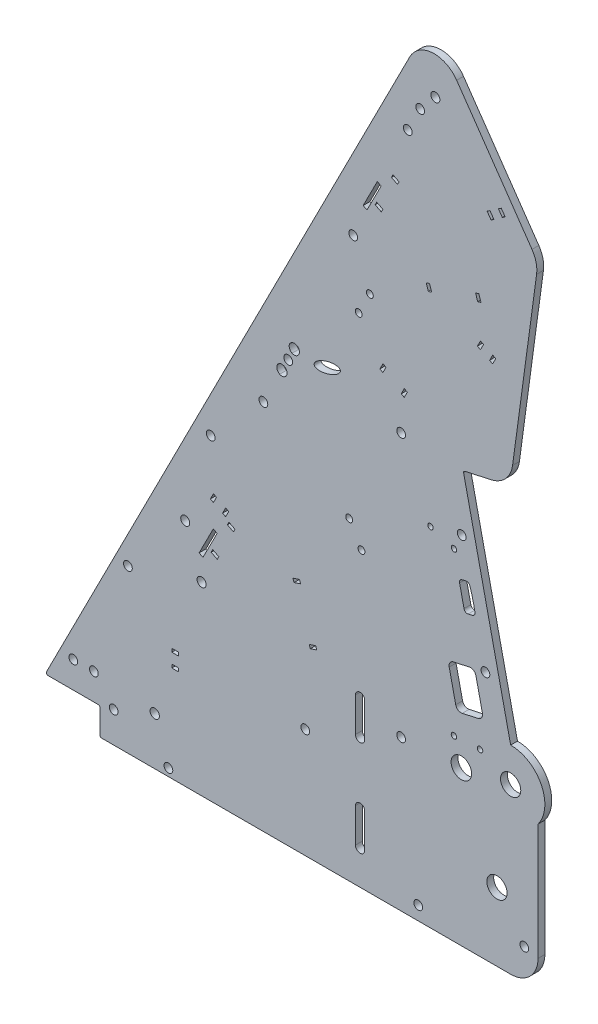
SolidWorks part; units mm, degrees
other "Markup1"
sketch "Sketch5"
ref_plane "Front Plane" through (0, 0, 0) normal (0, 0, 1) x (1, 0, 0)
ref_plane "Top Plane" through (0, 0, 0) normal (0, 1, 0) x (1, 0, 0)
ref_plane "Right Plane" through (0, 0, 0) normal (1, 0, 0) x (0, 0, -1)
sketch "Sketch1" plane through (0, 0, 0) normal (0, 0, 1) x (1, 0, 0)
  line L1 (228.6, -12.7) -> (228.6, 53.975)
  line L2 (178.7547, 351.4131) -> (0, 0)
  line L3 (228.6, 279.4) -> (178.7547, 351.4131)
  line L5 (0, 0) -> (25.4, 0)
  line L6 (25.4, 0) -> (25.4, -12.7)
  line L7 (25.4, -12.7) -> (228.6, -12.7)
  line L9 (215.9, 79.375) -> (193.9097, 178.5667)
  line L10 (193.9097, 178.5667) -> (215.6079, 183.377)
  line L11 (215.6079, 183.377) -> (228.6, 279.4)
  arc A0 (228.6, 53.975) -> (215.9, 79.375) centre (215.9, 63.5) ccw
  dimension "D7" = 12.7
  dimension "D8" = 76.2
  dimension "D10" = 31.75
  dimension "D2" = 292.1
  dimension "D3" = 25.4
  dimension "D4" = 215.9
  dimension "D5" = 394.2644
  dimension "D6" = 203.2
  dimension "D9" = 63.039
  dimension "D11" = 101.6
  dimension "D12" = 12.5
  dimension "D13" = 22.225
extrude "Boss-Extrude1" add sketch "Sketch1" along normal blind 3.175
sketch "Sketch2" plane through (0, 0, 3.175) normal (0, 0, 1) x (1, 0, 0)
  line L0 (178.7547, 351.4131) -> (0, 0) construction
  line L1 (25.4, -12.7) -> (228.6, -12.7) construction
  line L2 (215.9, 79.375) -> (193.9097, 178.5667) construction
  line L3 (193.9097, 178.5667) -> (215.6079, 183.377) construction
  line L4 (215.9, 79.375) -> (193.9097, 178.5667) construction
  line L5 (64.9432, 94.0578) -> (72.5445, 73.1732) construction
  line L6 (64.9432, 94.0578) -> (89.8317, 94.0578) construction
  line L10 (228.6, -12.7) -> (228.6, 53.975) construction
  circle A0 centre (64.9432, 94.0578) radius 2.0955
  circle A1 centre (180.975, 322.1643) radius 2.0955
  circle A2 centre (72.5445, 73.1732) radius 2.0955
  circle A3 centre (193.2078, 152.3944) radius 2.032
  circle A4 centre (215.9, 63.5) radius 4.699
  circle A7 centre (173.0375, -6.35) radius 2.032
  circle A8 centre (204.203, 102.7985) radius 2.032
  circle A26 centre (209.55, 19.05) radius 4.699
  arc A30 (228.6, 53.975) -> (215.9, 79.375) centre (215.9, 63.5) ccw construction
  circle A31 centre (165.1, 179.3875) radius 2.032
  dimension "D3" = 4.191
  dimension "D5" = 4.191
  dimension "D9" = 4.191
  dimension "D20" = 9.398
  dimension "D23" = 9.398
  dimension "D18" = 4.064
  dimension "D26" = 4.064
  dimension "D14" = 4.064
  dimension "D2" = 15.24
  dimension "D6" = 15.24
  dimension "D7" = 22.225
  dimension "D21" = 44.45
  dimension "D22" = 6.35
  dimension "D19" = 160.3375
  dimension "D24" = 44.45
  dimension "D25" = 6.35
  dimension "D27" = 25.4
  dimension "D28" = 50.8
  dimension "D29" = 6.35
  dimension "D17" = 6.35
  dimension "D33" = 55.5625
  dimension "D15" = 114.3
  dimension "D4" = 180.975
  dimension "D8" = 70
extrude "Cut-Extrude1" cut sketch "Sketch2" against normal through all
sketch "Sketch7" plane through (0, 0, 3.175) normal (0, 0, 1) x (1, 0, 0)
  line L0 (146.05, 3.175) -> (146.05, 19.05) construction
  line L1 (143.891, 3.175) -> (143.891, 19.05)
  line L2 (148.209, 3.175) -> (148.209, 19.05)
  line L3 (146.05, 47.625) -> (146.05, 63.5) construction
  line L4 (143.891, 47.625) -> (143.891, 63.5)
  line L5 (148.209, 47.625) -> (148.209, 63.5)
  line L6 (25.4, -12.7) -> (228.6, -12.7) construction
  line L12 (228.6, -12.7) -> (228.6, 53.975) construction
  line L13 (25.4, -12.7) -> (228.6, -12.7) construction
  arc A0 (143.891, 3.175) -> (148.209, 3.175) centre (146.05, 3.175) ccw
  arc A1 (148.209, 19.05) -> (143.891, 19.05) centre (146.05, 19.05) ccw
  arc A2 (143.891, 47.625) -> (148.209, 47.625) centre (146.05, 47.625) ccw
  arc A3 (148.209, 63.5) -> (143.891, 63.5) centre (146.05, 63.5) ccw
  circle A8 centre (50.8, 9.525) radius 2.159
  point P2 (146.05, 11.1125)
  point P9 (146.05, 55.5625)
  dimension "D1" = 4.318
  dimension "D5" = 4.318
  dimension "D2" = 15.875
  dimension "D3" = 15.875
  dimension "D4" = 44.45
  dimension "D6" = 95.25
  dimension "D7" = 82.55
  dimension "D8" = 15.875
  dimension "D9" = 22.225
extrude "Cut-Extrude2" cut sketch "Sketch7" against normal through all
sketch "Sketch10" plane through (0, 0, 3.175) normal (0, 0, 1) x (1, 0, 0)
  circle A1 centre (165.1, 57.15) radius 2.032
  circle A2 centre (120.65, 38.1) radius 2.032
  circle A3 centre (13.0465, 12.3347) radius 2.032
  circle A4 centre (22.5715, 12.3347) radius 2.032
  circle A5 centre (38.3604, 62.564) radius 2.032
  dimension "D1" = 4.064
  dimension "D2" = 4.064
  dimension "D4" = 63.5
  dimension "D5" = 69.85
extrude "Cut-Extrude3" cut sketch "Sketch10" against normal up to next
fillet "Fillet1" radius 12.7 4 edges at (228.6, -12.7, 1.5875) (178.7547, 351.4131, 1.5875) (215.6079, 183.377, 1.5875) (228.6, 279.4, 1.5875)
fillet "Fillet2" radius 0.7937 4 edges at (25.4, -12.7, 1.5875) (25.4, 0, 1.5875) (193.9097, 178.5667, 1.5875) (0, 0, 1.5875)
sketch "Sketch12" plane through (0, 0, 3.175) normal (0, 0, 1) x (1, 0, 0)
  circle A0 centre (31.75, 1.5875) radius 2.032
  circle A1 centre (222.25, 1.5875) radius 2.032
  circle A2 centre (57.15, -9.2075) radius 2.032
  circle A3 centre (57.15, -9.2075) radius 2.286 construction
  dimension "D1" = 4.064
  dimension "D2" = 4.064
extrude "Cut-Extrude5" cut sketch "Sketch12" against normal through all
sketch "Sketch13" plane through (0, 0, 3.175) normal (0, 0, 1) x (1, 0, 0)
  line L2 (194.6847, 178.7385) -> (206.9592, 181.4597) construction
  line L5 (199.2434, 101.699) -> (189.6226, 145.0954) construction
  line L6 (189.6022, 69.9806) -> (201.7089, 70.5092) construction
  line L7 (186.8444, 98.9502) -> (199.2434, 101.699)
  line L8 (186.8444, 98.9502) -> (190.9676, 80.3518)
  line L9 (190.9676, 80.3518) -> (203.3665, 83.1006)
  line L10 (199.2434, 101.699) -> (203.3665, 83.1006)
  line L11 (189.6022, 69.9806) -> (190.9676, 80.3518) construction
  line L12 (201.7089, 70.5092) -> (203.3665, 83.1006) construction
  line L13 (215.9, 79.375) -> (194.0815, 177.7917) construction
  line L14 (178.7216, 148.5324) -> (189.6226, 145.0954) construction
  line L15 (195.1281, 134.9336) -> (193.4153, 134.5539)
  line L16 (192.209, 132.6604) -> (194.2706, 123.3612)
  line L17 (196.1641, 122.1549) -> (198.1091, 122.5861)
  line L18 (211.4332, 99.5233) -> (205.2337, 98.1489) construction
  line L19 (198.3765, 158.4184) -> (211.4332, 99.5233) construction
  circle A0 centre (189.6022, 69.9806) radius 1.27
  circle A1 centre (201.7089, 70.5092) radius 1.27
  circle A2 centre (178.7216, 148.5324) radius 1.27
  circle A3 centre (189.6226, 145.0954) radius 1.27
  arc A4 (199.3306, 124.402) -> (196.9796, 133.88) centre (134.9024, 113.4517) ccw
  arc A6 (199.4957, 103.5221) -> (189.2475, 149.7492) centre (134.9024, 113.4517) ccw construction
  arc A7 (195.1281, 134.9336) -> (196.9796, 133.88) centre (195.4717, 133.3837) cw
  arc A8 (198.1091, 122.5861) -> (199.3306, 124.402) centre (197.7655, 124.136) ccw
  arc A9 (194.2706, 123.3612) -> (196.1641, 122.1549) centre (195.8205, 123.7048) ccw
  arc A10 (193.4153, 134.5539) -> (192.209, 132.6604) centre (193.7589, 133.004) ccw
  point P26 (208.3335, 98.8361)
  point P31 (196.515, 135.2411)
  point P36 (194.6142, 121.8113)
  point P39 (191.8654, 134.2103)
  dimension "D7" = 2.54
  dimension "D16" = 1.5875
  dimension "D2" = 11.43
  dimension "D3" = 76.2
  dimension "D4" = 12.7
  dimension "D5" = 19.05
  dimension "D6" = 120
  dimension "D8" = 110
  dimension "D9" = 80
  dimension "D10" = 12.7
  dimension "D11" = 44.45
  dimension "D12" = 11.43
  dimension "D13" = 12.7
  dimension "D14" = 4.7625
  dimension "D15" = 38.1
extrude "Cut-Extrude6" cut sketch "Sketch13" against normal through all both and the other way through all
sketch "Sketch14" plane through (0, 0, 3.175) normal (0, 0, 1) x (1, 0, 0)
  line L0 (26.1937, -12.7) -> (215.9, -12.7) construction
  line L1 (228.6, 0) -> (228.6, 53.975) construction
  line L2 (112.7125, 182.5625) -> (101.1964, 159.9231) construction
  line L3 (169.1053, 332.4434) -> (0.5868, 1.1536) construction
  line L4 (112.7125, 182.5625) -> (136.864, 190.4279) construction
  line L5 (147.4827, 261.9243) -> (154.0469, 274.8287)
  line L6 (147.4827, 261.9243) -> (149.2654, 261.0175)
  line L7 (154.0469, 274.8287) -> (155.8295, 273.922)
  line L8 (149.2654, 261.0175) -> (155.8295, 273.922)
  line L9 (169.1053, 332.4434) -> (0.5868, 1.1536) construction
  line L10 (160.5905, 279.7801) -> (161.3102, 281.1951)
  line L11 (160.5905, 279.7801) -> (163.4204, 278.3406)
  line L12 (161.3102, 281.1951) -> (164.1402, 279.7556)
  line L13 (163.4204, 278.3406) -> (164.1402, 279.7556)
  line L14 (153.7897, 266.4104) -> (156.6196, 264.9709)
  line L15 (153.7897, 266.4104) -> (153.0699, 264.9954)
  line L16 (156.6196, 264.9709) -> (155.8998, 263.5559)
  line L17 (153.0699, 264.9954) -> (155.8998, 263.5559)
  line L19 (178.2697, 245.9923) -> (179.2404, 242.9693)
  line L20 (178.2697, 245.9923) -> (176.7582, 245.5069)
  line L21 (179.2404, 242.9693) -> (177.7289, 242.4839)
  line L22 (176.7582, 245.5069) -> (177.7289, 242.4839)
  line L24 (200.6096, 249.8308) -> (199.639, 252.8538)
  line L25 (200.6096, 249.8308) -> (202.1211, 250.3161)
  line L26 (199.639, 252.8538) -> (201.1505, 253.3391)
  line L27 (202.1211, 250.3161) -> (201.1505, 253.3391)
  line L34 (77.9534, 97.2255) -> (79.736, 96.3187)
  line L47 (77.9534, 97.2255) -> (71.3892, 84.3211)
  line L56 (79.736, 96.3187) -> (73.1718, 83.4143)
  line L57 (71.3892, 84.3211) -> (73.1718, 83.4143)
  line L58 (85.2167, 103.5918) -> (84.497, 102.1769)
  line L59 (85.2167, 103.5918) -> (88.0466, 102.1523)
  line L60 (84.497, 102.1769) -> (87.3269, 100.7374)
  line L61 (88.0466, 102.1523) -> (87.3269, 100.7374)
  line L62 (156.643, 199.3999) -> (158.0826, 202.2298)
  line L63 (156.643, 199.3999) -> (155.2281, 200.1197)
  line L64 (158.0826, 202.2298) -> (156.6676, 202.9496)
  line L65 (155.2281, 200.1197) -> (156.6676, 202.9496)
  line L66 (165.1328, 195.0814) -> (166.5723, 197.9113)
  line L67 (165.1328, 195.0814) -> (166.5478, 194.3617)
  line L68 (166.5723, 197.9113) -> (167.9873, 197.1916)
  line L69 (166.5478, 194.3617) -> (167.9873, 197.1916)
  line L78 (77.6961, 88.8072) -> (76.9764, 87.3922)
  line L79 (201.9154, 234.7497) -> (200.4759, 231.9198)
  line L80 (201.9154, 234.7497) -> (203.3303, 234.0299)
  line L81 (200.4759, 231.9198) -> (201.8908, 231.2)
  line L82 (203.3303, 234.0299) -> (201.8908, 231.2)
  line L83 (206.1357, 229.0407) -> (207.5752, 231.8707)
  line L84 (206.1357, 229.0407) -> (207.5507, 228.321)
  line L85 (207.5752, 231.8707) -> (208.9902, 231.1509)
  line L86 (207.5507, 228.321) -> (208.9902, 231.1509)
  line L88 (205.014, 288.3715) -> (206.821, 285.7609)
  line L89 (205.014, 288.3715) -> (206.3193, 289.275)
  line L90 (206.821, 285.7609) -> (208.1263, 286.6644)
  line L91 (206.3193, 289.275) -> (208.1263, 286.6644)
  line L92 (210.2352, 291.9855) -> (212.0422, 289.3749)
  line L93 (210.2352, 291.9855) -> (211.5405, 292.889)
  line L94 (212.0422, 289.3749) -> (213.3475, 290.2784)
  line L95 (211.5405, 292.889) -> (213.3475, 290.2784)
  line L96 (225.7968, 283.4499) -> (190.8675, 333.9133) construction
  line L97 (77.6961, 88.8072) -> (80.5261, 87.3677)
  line L98 (76.9764, 87.3922) -> (79.8063, 85.9527)
  line L99 (80.5261, 87.3677) -> (79.8063, 85.9527)
  line L100 (122.4534, 73.1037) -> (122.9512, 71.5963)
  line L101 (122.4534, 73.1037) -> (125.4682, 74.0993)
  line L102 (122.9512, 71.5963) -> (125.9661, 72.5919)
  line L103 (125.4682, 74.0993) -> (125.9661, 72.5919)
  line L104 (114.9173, 95.9228) -> (115.4151, 94.4154)
  line L105 (114.9173, 95.9228) -> (117.9322, 96.9185)
  line L106 (115.4151, 94.4154) -> (118.43, 95.411)
  line L107 (117.9322, 96.9185) -> (118.43, 95.411)
  line L108 (73.3338, 88.1438) -> (77.899, 97.1186) construction
  line L109 (75.1164, 87.2371) -> (79.6816, 96.2118) construction
  line L110 (76.2812, 89.5269) -> (86.5313, 84.313) construction
  line L111 (83.082, 102.8966) -> (93.3321, 97.6827) construction
  line L112 (121.934, 72.0825) -> (123.4755, 75.113) construction
  line L113 (127.9171, 72.8537) -> (123.4755, 75.113) construction
  line L114 (112.3753, 83.5081) -> (119.5388, 97.5909) construction
  line L115 (112.1491, 96.0767) -> (117.4079, 93.4017) construction
  line L116 (149.0052, 264.9173) -> (147.5544, 262.0651) construction
  line L117 (150.7878, 264.0106) -> (151.2099, 264.8403) construction
  line L118 (162.6248, 261.9162) -> (152.3747, 267.1302) construction
  line L119 (169.4256, 275.2859) -> (159.1755, 280.4999) construction
  line L120 (199.3876, 252.3597) -> (200.1584, 253.8749) construction
  line L121 (198.6169, 250.8445) -> (203.0585, 248.5852) construction
  line L122 (203.2698, 247.9167) -> (195.3067, 232.262) construction
  line L123 (180.2625, 244.9786) -> (175.0037, 247.6536) construction
  line L124 (178.1316, 240.7894) -> (185.2951, 254.8722) construction
  line L125 (190.7763, 226.1672) -> (185.5176, 228.8422) construction
  line L126 (58.7375, 39.6875) -> (61.9125, 39.6875)
  line L127 (58.7375, 39.6875) -> (58.7375, 38.1)
  line L128 (61.9125, 39.6875) -> (61.9125, 38.1)
  line L129 (58.7375, 38.1) -> (61.9125, 38.1)
  line L130 (58.7375, 33.3375) -> (61.9125, 33.3375)
  line L131 (58.7375, 33.3375) -> (58.7375, 31.75)
  line L132 (61.9125, 33.3375) -> (61.9125, 31.75)
  line L133 (58.7375, 31.75) -> (61.9125, 31.75)
  line L135 (78.0516, 111.4242) -> (76.6121, 108.5943)
  line L136 (78.0516, 111.4242) -> (79.4665, 110.7045)
  line L137 (76.6121, 108.5943) -> (78.027, 107.8745)
  line L138 (79.4665, 110.7045) -> (78.027, 107.8745)
  line L139 (82.2719, 105.7153) -> (83.7114, 108.5452)
  line L140 (82.2719, 105.7153) -> (83.6869, 104.9955)
  line L141 (83.7114, 108.5452) -> (85.1264, 107.8254)
  line L142 (83.6869, 104.9955) -> (85.1264, 107.8254)
  circle A0 centre (142.875, 247.65) radius 2.032
  circle A1 centre (112.7125, 182.5625) radius 2.032
  circle A2 centre (101.1964, 159.9231) radius 2.032
  circle A3 centre (150.594, 227.8985) radius 1.6 construction
  circle A4 centre (145.4254, 217.7376) radius 1.6 construction
  circle A5 centre (141.0058, 132.9805) radius 1.6 construction
  circle A6 centre (146.7058, 123.1078) radius 1.6 construction
  circle A7 centre (150.594, 227.8985) radius 1.6
  circle A8 centre (145.4254, 217.7376) radius 1.6
  circle A9 centre (141.0058, 132.9805) radius 1.6
  circle A10 centre (146.7058, 123.1078) radius 1.6
  arc A13 (0, 1.5875) -> (1.5875, 0) centre (1.5875, 1.5875) ccw construction
  ellipse E0 centre (109.8335, 176.9027) end of major axis (108.7539, 174.7802) minor radius 2.32 (108.7539, 174.7802) -> (110.9131, 179.0251) ccw construction
  ellipse E1 centre (109.8335, 176.9027) end of major axis (108.7539, 174.7802) minor radius 2.32 (108.7539, 174.7802) -> (110.9131, 179.0251) ccw
  ellipse E2 centre (130.8261, 188.4615) end of major axis (124.7883, 186.4952) minor radius 2.3812
  ellipse E3 centre (115.5915, 188.2223) end of major axis (114.5119, 186.0999) minor radius 2.32 (114.5119, 186.0999) -> (116.6711, 190.3448) ccw construction
  ellipse E4 centre (115.5915, 188.2223) end of major axis (114.5119, 186.0999) minor radius 2.32 (114.5119, 186.0999) -> (116.6711, 190.3448) ccw
  spline S0 degree 3 poles (603.8918, 1049.0657) (-166.9189, -675.3083) (147.8077, 168.3802) (110.3225, 179.2425) (110.1654, 179.2721) (109.6955, 179.3152) (109.3734, 179.2831) (108.9218, 179.1456) (108.7737, 179.0841) (108.4954, 178.9343) (108.365, 178.8464) (108.1219, 178.6442) (108.0097, 178.5297) (107.8134, 178.2839) (107.7278, 178.1512) (107.5834, 177.8672) (107.527, 177.7202) (107.4441, 177.4168) (107.4178, 177.2585) (107.3978, 176.9432) (107.4036, 176.7863) (107.4465, 176.4736) (107.4841, 176.3175) (107.5874, 176.0205) (107.6532, 175.8777) (107.8133, 175.6037) (107.9066, 175.4748) (114.8282, 167.6036) (173.9427, 200.577) (-567.4982, 911.3293) knots -15.287416 -15.287416 -15.287416 -15.287416 0.0625 0.0625 0.125 0.125 0.25 0.25 0.3125 0.3125 0.375 0.375 0.4375 0.4375 0.5 0.5 0.5625 0.5625 0.625 0.625 0.6875 0.6875 0.75 0.75 0.8125 0.8125 0.875 0.875 4.983329 4.983329 4.983329 4.983329 only from (110.9131, 179.0251) to (108.7539, 174.7802) construction
  spline S1 degree 3 poles (110.9131, 179.0251) (110.7727, 179.0965) (110.6265, 179.1544) (110.3225, 179.2425) (110.1654, 179.2721) (109.6955, 179.3152) (109.3734, 179.2831) (108.9218, 179.1456) (108.7737, 179.0841) (108.4954, 178.9343) (108.365, 178.8464) (108.1219, 178.6442) (108.0097, 178.5297) (107.8134, 178.2839) (107.7278, 178.1512) (107.5834, 177.8672) (107.527, 177.7202) (107.4441, 177.4168) (107.4178, 177.2585) (107.3978, 176.9432) (107.4036, 176.7863) (107.4465, 176.4736) (107.4841, 176.3175) (107.5874, 176.0205) (107.6532, 175.8777) (107.8133, 175.6037) (107.9066, 175.4748) (108.2178, 175.121) (108.4736, 174.9228) (108.7539, 174.7802) knots 0 0 0 0 0.0625 0.0625 0.125 0.125 0.25 0.25 0.3125 0.3125 0.375 0.375 0.4375 0.4375 0.5 0.5 0.5625 0.5625 0.625 0.625 0.6875 0.6875 0.75 0.75 0.8125 0.8125 0.875 0.875 1 1 1 1
  spline S2 degree 3 poles (-635.3332, 847.705) (160.0375, 206.8561) (120.8424, 181.1302) (113.9875, 186.4501) (113.8729, 186.5577) (113.5583, 186.9155) (113.3974, 187.1901) (113.2413, 187.6401) (113.2046, 187.793) (113.1618, 188.1044) (113.1558, 188.2648) (113.176, 188.5797) (113.2018, 188.7347) (113.2848, 189.0394) (113.3426, 189.1891) (113.5563, 189.6095) (113.7586, 189.8627) (114.1212, 190.1647) (114.2542, 190.2544) (114.5324, 190.4041) (114.6775, 190.4645) (114.9798, 190.5567) (115.1369, 190.5882) (115.4499, 190.6199) (115.6074, 190.6207) (115.9244, 190.5918) (116.0795, 190.5623) (125.0451, 187.9725) (125.4505, 134.6135) (-868.6048, 361.2821) knots -3.325634 -3.325634 -3.325634 -3.325634 0.0625 0.0625 0.125 0.125 0.25 0.25 0.3125 0.3125 0.375 0.375 0.4375 0.4375 0.5 0.5 0.625 0.625 0.6875 0.6875 0.75 0.75 0.8125 0.8125 0.875 0.875 0.9375 0.9375 4.586013 4.586013 4.586013 4.586013 only from (114.5119, 186.0999) to (116.6711, 190.3448) construction
  spline S3 degree 3 poles (114.5119, 186.0999) (114.3711, 186.1715) (114.2359, 186.2574) (113.9875, 186.4501) (113.8729, 186.5577) (113.5583, 186.9155) (113.3974, 187.1901) (113.2413, 187.6401) (113.2046, 187.793) (113.1618, 188.1044) (113.1558, 188.2648) (113.176, 188.5797) (113.2018, 188.7347) (113.2848, 189.0394) (113.3426, 189.1891) (113.5563, 189.6095) (113.7586, 189.8627) (114.1212, 190.1647) (114.2542, 190.2544) (114.5324, 190.4041) (114.6775, 190.4645) (114.9798, 190.5567) (115.1369, 190.5882) (115.4499, 190.6199) (115.6074, 190.6207) (115.9244, 190.5918) (116.0795, 190.5623) (116.3815, 190.4751) (116.53, 190.4166) (116.6711, 190.3448) knots 0 0 0 0 0.0625 0.0625 0.125 0.125 0.25 0.25 0.3125 0.3125 0.375 0.375 0.4375 0.4375 0.5 0.5 0.625 0.625 0.6875 0.6875 0.75 0.75 0.8125 0.8125 0.875 0.875 0.9375 0.9375 1 1 1 1
  point P179 (82.9794, 105.3554)
  dimension "D1" = 4.064
  dimension "D15" = 3.175
  dimension "D2" = 195.2625
  dimension "D3" = 115.8875
  dimension "D4" = 85.725
  dimension "D5" = 260.35
  dimension "D6" = 25.4
  dimension "D7" = 4.7625
  dimension "D8" = 12.7
  dimension "D9" = 19.05
  dimension "D10" = 45
  dimension "D11" = 6.858
  dimension "D12" = 7.62
  dimension "D13" = 3.175
  dimension "D14" = 1.5875
  dimension "D16" = 1.5875
  dimension "D17" = 1.5875
  dimension "D18" = 9.525
  dimension "D19" = 47.625
  dimension "D20" = 38.1
  dimension "D21" = 6.858
  dimension "D22" = 7.62
  dimension "D23" = 1.5875
  dimension "D24" = 3.175
  dimension "D25" = 1.5875
  dimension "D26" = 4.7625
  dimension "D27" = 4.7625
  dimension "D28" = 1.5875
  dimension "D29" = 3.175
  dimension "D30" = 9.525
  dimension "D31" = 4.7625
  dimension "D32" = 4.7625
  dimension "D33" = 1.5875
  dimension "D34" = 3.175
  dimension "D35" = 6.35
  dimension "D36" = 12.7
  dimension "D37" = 1.5875
  dimension "D38" = 3.175
  dimension "D39" = 9.525
  dimension "D40" = 57.15
  dimension "D41" = 44.45
  dimension "D42" = 1.5875
  dimension "D43" = 4.7625
  dimension "D44" = 3.175
extrude "Cut-Extrude7" cut sketch "Sketch14" against normal through all
sketch "Sketch15" plane through (0, 0, 3.175) normal (0, 0, 1) x (1, 0, 0)
  line L0 (169.1053, 332.4434) -> (0.5868, 1.1536) construction
  circle A0 centre (76.7868, 134.1481) radius 2.032
  circle A1 centre (173.9472, 313.9507) radius 2.032
  circle A2 centre (168.1892, 302.631) radius 2.032
  circle A3 centre (173.9472, 313.9507) radius 1.905 construction
  circle A4 centre (168.1892, 302.631) radius 1.905 construction
  dimension "D1" = 4.064
  dimension "D4" = 4.064
  dimension "D2" = 7.62
  dimension "D3" = 76.2
extrude "Cut-Extrude8" cut sketch "Sketch15" against normal through all
fillet "Fillet3" radius 2.54 4 edges at (199.2434, 101.699, 1.5875) (186.8444, 98.9502, 1.5875) (190.9676, 80.3518, 1.5875) (203.3665, 83.1006, 1.5875)
sketch "Sketch16" plane through (0, 0, 3.175) normal (0, 0, 1) x (1, 0, 0)
  line L0 (228.6, 0) -> (228.6, 53.975) construction
  line L1 (26.1937, -12.7) -> (215.9, -12.7) construction
  circle A0 centre (193.04, 58.801) radius 4.7625
  dimension "D1" = 9.525
  dimension "D2" = 35.56
  dimension "D3" = 71.501
extrude "Cut-Extrude9" cut sketch "Sketch16" against normal through all
equation "\"D6@Sketch2\"=\"D2@Sketch2\""
